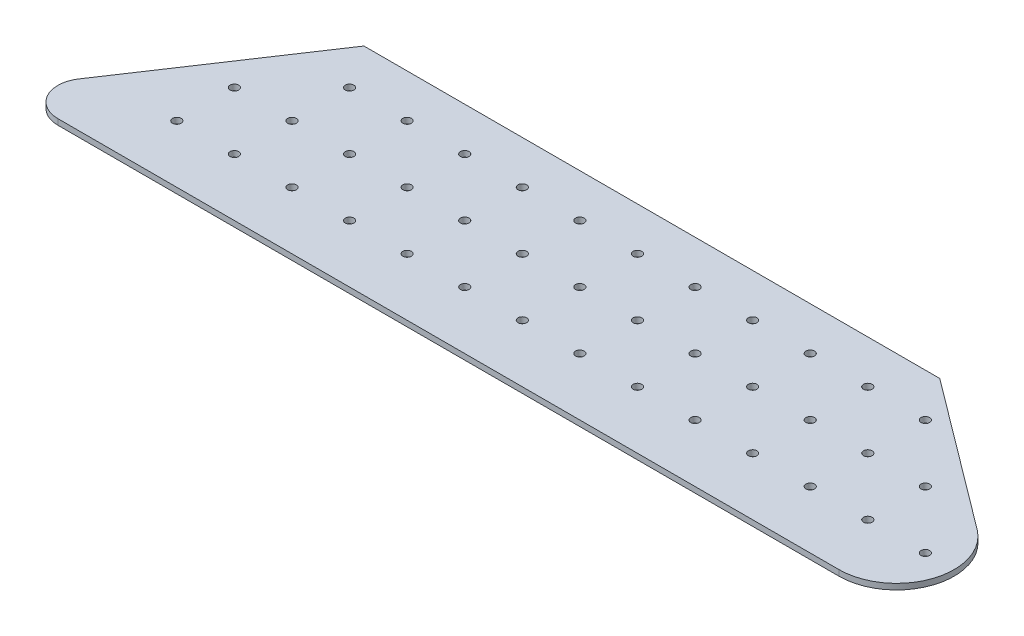
SolidWorks part; units mm, degrees
ref_plane "Front Plane" through (0, 0, 0) normal (0, 0, 1) x (1, 0, 0)
ref_plane "Top Plane" through (0, 0, 0) normal (0, 1, 0) x (1, 0, 0)
ref_plane "Right Plane" through (0, 0, 0) normal (1, 0, 0) x (0, 0, -1)
sketch "Sketch1" plane through (0, 0, 0) normal (0, 1, 0) x (1, 0, 0)
  line L0 (-17.984, 0) -> (332.016, 0)
  line L1 (-55, 0) -> (55, 0) construction
  line L2 (332.016, 0) -> (232.016, 75)
  line L3 (232.016, 75) -> (32.016, 75)
  line L4 (32.016, 75) -> (-17.984, 0)
  line L5 (-45.5557, 20) -> (286.5842, 20) construction
  line L6 (-34.9172, 40) -> (80.516, 40) construction
  line L7 (-27.9699, 60) -> (20.516, 60) construction
  line L8 (305.3493, 20) -> (439.4037, 20) construction
  line L9 (123.516, 40) -> (160.516, 40) construction
  line L10 (163.516, 40) -> (200.516, 40) construction
  line L11 (203.516, 40) -> (233.588, 40) construction
  line L12 (236.588, 40) -> (263.1596, 40) construction
  line L13 (266.1596, 40) -> (280.516, 40) construction
  line L14 (236.588, 60) -> (319.174, 60) construction
  line L15 (203.516, 60) -> (233.588, 60) construction
  line L16 (163.516, 60) -> (200.516, 60) construction
  line L17 (123.516, 60) -> (160.516, 60) construction
  line L18 (83.516, 60) -> (120.516, 60) construction
  line L19 (43.516, 60) -> (80.516, 60) construction
  line L20 (83.516, 40) -> (120.516, 40) construction
  line L21 (242.016, 20) -> (242.016, 12.284) construction
  line L22 (76.4385, 30) -> (108.1697, 30) construction
  line L23 (283.516, 40) -> (434.9926, 40) construction
  circle A0 centre (42.016, 20) radius 1.5
  circle A1 centre (62.016, 20) radius 1.5
  circle A2 centre (82.016, 20) radius 1.5
  circle A3 centre (102.016, 20) radius 1.5
  circle A4 centre (122.016, 20) radius 1.5
  circle A21 centre (22.016, 20) radius 1.5
  circle A22 centre (162.016, 20) radius 1.5
  circle A23 centre (182.016, 20) radius 1.5
  circle A24 centre (202.016, 20) radius 1.5
  circle A25 centre (222.016, 20) radius 1.5
  circle A26 centre (242.016, 20) radius 1.5
  circle A27 centre (142.016, 20) radius 1.5
  circle A28 centre (242.016, 60) radius 1.5
  circle A29 centre (222.016, 60) radius 1.5
  circle A30 centre (202.016, 60) radius 1.5
  circle A31 centre (182.016, 60) radius 1.5
  circle A32 centre (162.016, 60) radius 1.5
  circle A33 centre (142.016, 60) radius 1.5
  circle A34 centre (122.016, 60) radius 1.5
  circle A35 centre (102.016, 60) radius 1.5
  circle A36 centre (82.016, 60) radius 1.5
  circle A37 centre (62.016, 60) radius 1.5
  circle A38 centre (42.016, 60) radius 1.5
  circle A41 centre (282.016, 20) radius 1.5
  circle A42 centre (262.016, 20) radius 1.5
  circle A44 centre (262.016, 40) radius 1.5
  circle A45 centre (242.016, 40) radius 1.5
  circle A46 centre (202.016, 40) radius 1.5
  circle A47 centre (182.016, 40) radius 1.5
  circle A48 centre (162.016, 40) radius 1.5
  circle A49 centre (142.016, 40) radius 1.5
  circle A50 centre (122.016, 40) radius 1.5
  circle A51 centre (102.016, 40) radius 1.5
  circle A52 centre (82.016, 40) radius 1.5
  circle A53 centre (62.016, 40) radius 1.5
  circle A54 centre (42.016, 40) radius 1.5
  circle A55 centre (22.016, 40) radius 1.5
  circle A56 centre (222.016, 40) radius 1.5
  dimension "D13" = 3
  dimension "D14" = 3
  dimension "D15" = 3
  dimension "D16" = 3
  dimension "D17" = 3
  dimension "D18" = 20
  dimension "D19" = 10
  dimension "D20" = 40
  dimension "D21" = 60
  dimension "D22" = 80
  dimension "D23" = 100
  dimension "D24" = 20
  dimension "D25" = 0
  dimension "D28" = 3
  dimension "D34" = 20
  dimension "D1" = 350
  dimension "D2" = 75
  dimension "D3" = 100
  dimension "D4" = 200
  dimension "D5" = 20
  dimension "D6" = 40
  dimension "D7" = 60
  dimension "D8" = 60
  dimension "D9" = 80
  dimension "D10" = 100
  dimension "D11" = 120
  dimension "D12" = 140
extrude "Boss-Extrude1" add sketch "Sketch1" along normal blind 2
fillet "Fillet4" radius 20 1 edges at (332.016, 1, 0)
fillet "Fillet5" radius 10 1 edges at (-17.984, 1, 0)
